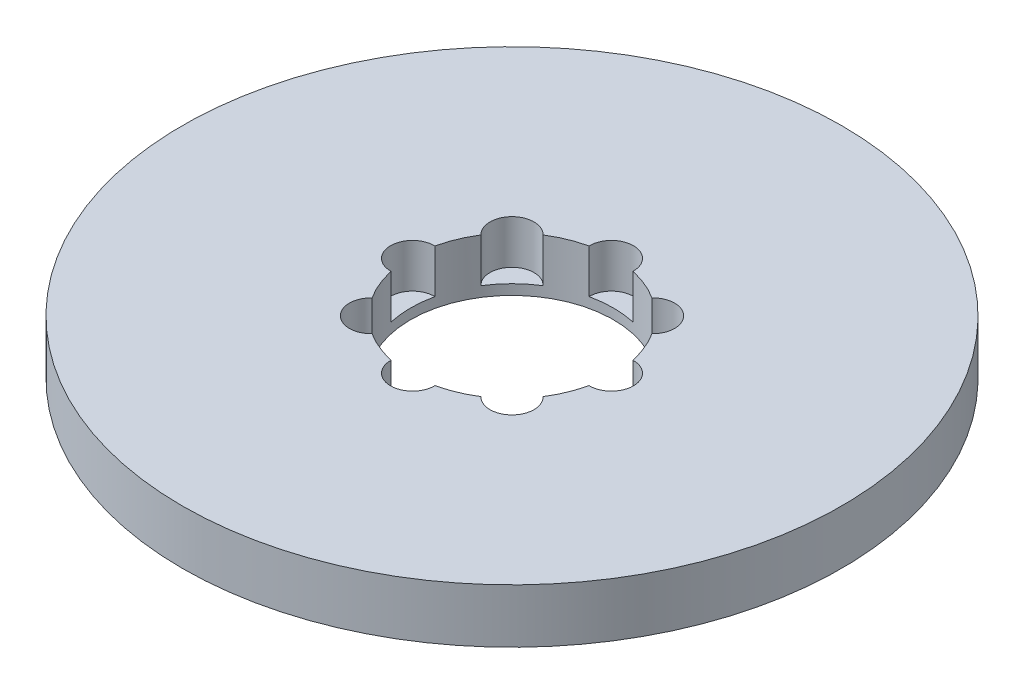
SolidWorks part; units mm, degrees
ref_plane "Front Plane" through (0, 0, 0) normal (0, 0, 1) x (1, 0, 0)
ref_plane "Top Plane" through (0, 0, 0) normal (0, 1, 0) x (1, 0, 0)
ref_plane "Right Plane" through (0, 0, 0) normal (1, 0, 0) x (0, 0, -1)
sketch "Sketch1" plane through (0, 0, 0) normal (0, 1, 0) x (1, 0, 0)
  circle A0 centre (0, 0) radius 97.5
  dimension "FLANGE_OD" = 195
extrude "Boss-Extrude1" add sketch "Sketch1" along normal blind 16
sketch "Sketch2" plane through (0, 0, 0) normal (0, 1, 0) x (1, 0, 0)
  circle A0 centre (0, 0) radius 30
  dimension "BORE_D" = 60
extrude "Cut-Extrude1" cut sketch "Sketch2" along normal through all
sketch "Sketch3" plane through (0, 16, 0) normal (0, 1, 0) x (1, 0, 0)
  circle A0 centre (0, 0) radius 29.4288 construction
  circle A1 centre (-29.4288, 0) radius 6.4976
  dimension "BOLT_D" = 12.9953
  dimension "BOLT_PCD" = 58.8577
extrude "Cut-Extrude2" cut sketch "Sketch3" against normal blind 12.9852
pattern_circular "CirPattern1" count 8 over 360 about axis through (0, 0, 0) along (0, 1, 0) of "Cut-Extrude2"
